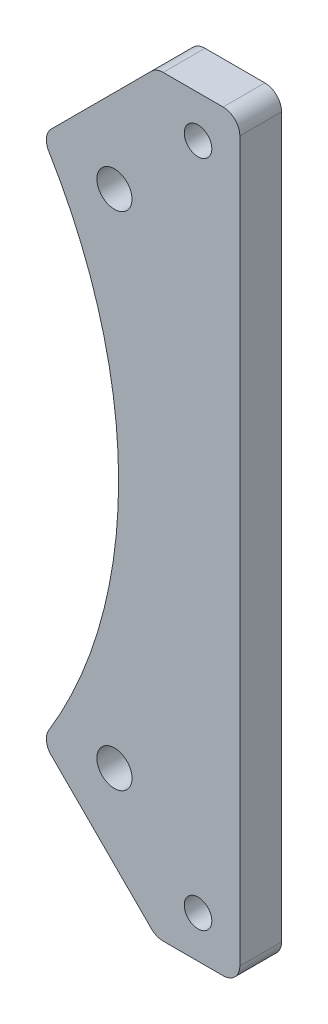
SolidWorks part; units mm, degrees
material "5052-H34"
ref_plane "正面" through (0, 0, 0) normal (0, 0, 1) x (1, 0, 0)
ref_plane "平面" through (0, 0, 0) normal (0, 1, 0) x (1, 0, 0)
ref_plane "右側面" through (0, 0, 0) normal (1, 0, 0) x (0, 0, -1)
sketch "ｽｹｯﾁ1" plane through (0, 0, 0) normal (0, 0, 1) x (1, 0, 0)
  line L0 (0, 0) -> (57.5, 0) construction
  line L1 (-57.5, 30) -> (57.5, 30) construction
  line L2 (-57.5, 30) -> (-57.5, -30) construction
  line L3 (-57.5, -30) -> (57.5, -30) construction
  line L4 (57.5, 30) -> (57.5, -30) construction
  line L5 (-57.5, 30) -> (57.5, -30) construction
  line L6 (-57.5, -30) -> (57.5, 30) construction
  line L7 (72.5, 45) -> (72.5, -45)
  line L8 (72.5, -45) -> (62.5, -45)
  line L9 (62.5, -45) -> (48.8179, -31.3179)
  line L10 (62.5, 45) -> (48.8179, 31.3179)
  line L11 (72.5, 45) -> (62.5, 45)
  circle A0 centre (57.5, 30) radius 2.1
  circle A1 centre (57.5, -30) radius 2.1
  circle A2 centre (67.5, 40) radius 1.65
  circle A3 centre (67.5, -40) radius 1.65
  circle A4 centre (0, 0) radius 58
  point P0 (0, 0)
  point P15 (47.9754, -32.5939)
  point P22 (72.5, 48.1033)
  point P23 (47.0892, -33.8616)
  dimension "D3" = 4.2
  dimension "D4" = 3.3
  dimension "D7" = 116
  dimension "D1" = 115
  dimension "D2" = 60
  dimension "D5" = 10
  dimension "D6" = 80
  dimension "D8" = 5
  dimension "D9" = 5
  dimension "D10" = 135
  dimension "D11" = 10
extrude "ﾎﾞｽ - 押し出し1" add sketch "ｽｹｯﾁ1" along normal blind 5 contours A4 L9 L8 L7 L11 L10 A0 A1 A2 A3 region at (63.6457, 0, 0)
fillet "ﾌｨﾚｯﾄ1" radius 2 6 edges at (62.5, 45, 2.5) (48.8179, 31.3179, 2.5) (48.8179, -31.3179, 2.5) (62.5, -45, 2.5) (72.5, -45, 2.5) (72.5, 45, 2.5)
